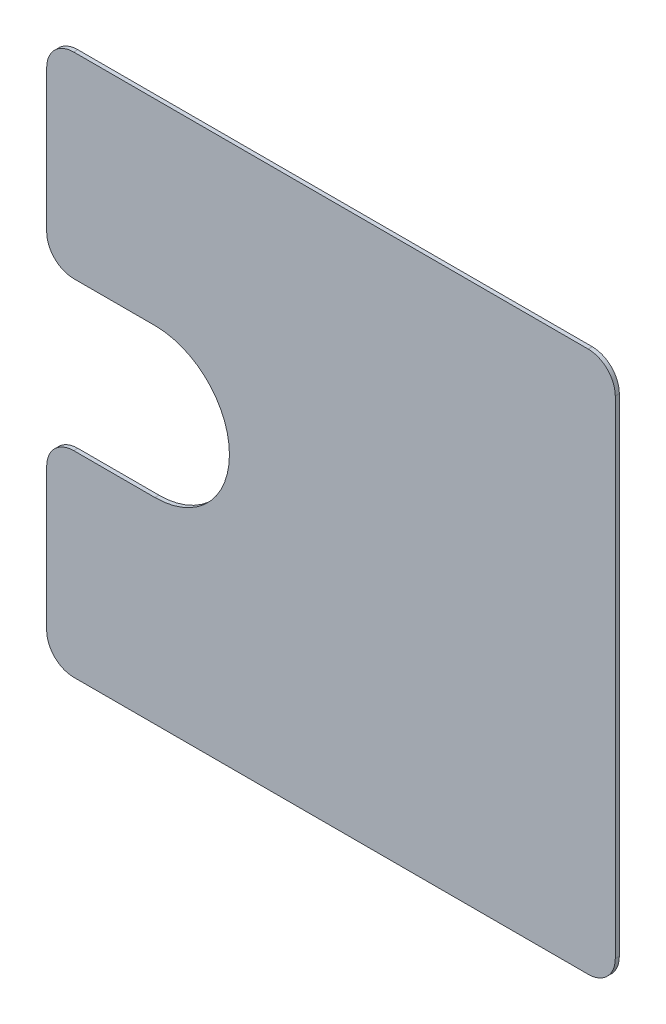
SolidWorks part; units mm, degrees
ref_plane "前视基准面" through (0, 0, 0) normal (0, 0, 1) x (1, 0, 0)
ref_plane "上视基准面" through (0, 0, 0) normal (0, 1, 0) x (1, 0, 0)
ref_plane "右视基准面" through (0, 0, 0) normal (1, 0, 0) x (0, 0, -1)
other "Configuration Table"
sketch "草图1" plane through (0, 0, 0) normal (0, 0, 1) x (1, 0, 0)
  line L0 (-130, 55) -> (-210, 55)
  line L1 (-190, -200) -> (190, -200)
  line L2 (-210, -180) -> (-210, -55)
  line L3 (-190, 200) -> (190, 200)
  line L4 (210, -180) -> (210, 180)
  line L5 (-210, -200) -> (210, 200) construction
  line L6 (-210, 200) -> (210, -200) construction
  line L7 (-130, -55) -> (-210, -55)
  line L8 (-210, 55) -> (-210, 180)
  line L9 (0, 0) -> (-50000, 0) construction
  arc A0 (-130, -55) -> (-130, 55) centre (-130, 0) ccw
  arc A1 (190, -200) -> (210, -180) centre (190, -180) ccw
  arc A2 (-190, -200) -> (-210, -180) centre (-190, -180) cw
  arc A3 (-210, 180) -> (-190, 200) centre (-190, 180) cw
  arc A4 (190, 200) -> (210, 180) centre (190, 180) cw
  point P0 (0, 0)
  point P9 (0, 0)
  dimension "D3" = 110
  dimension "D4" = 20
  dimension "D1" = 420
  dimension "D2" = 400
  dimension "D5" = 80
extrude "凸台-拉伸1" add sketch "草图1" along normal blind 3
fillet "圆角1" radius 20 2 edges at (-210, -55, 1.5) (-210, 55, 1.5)
